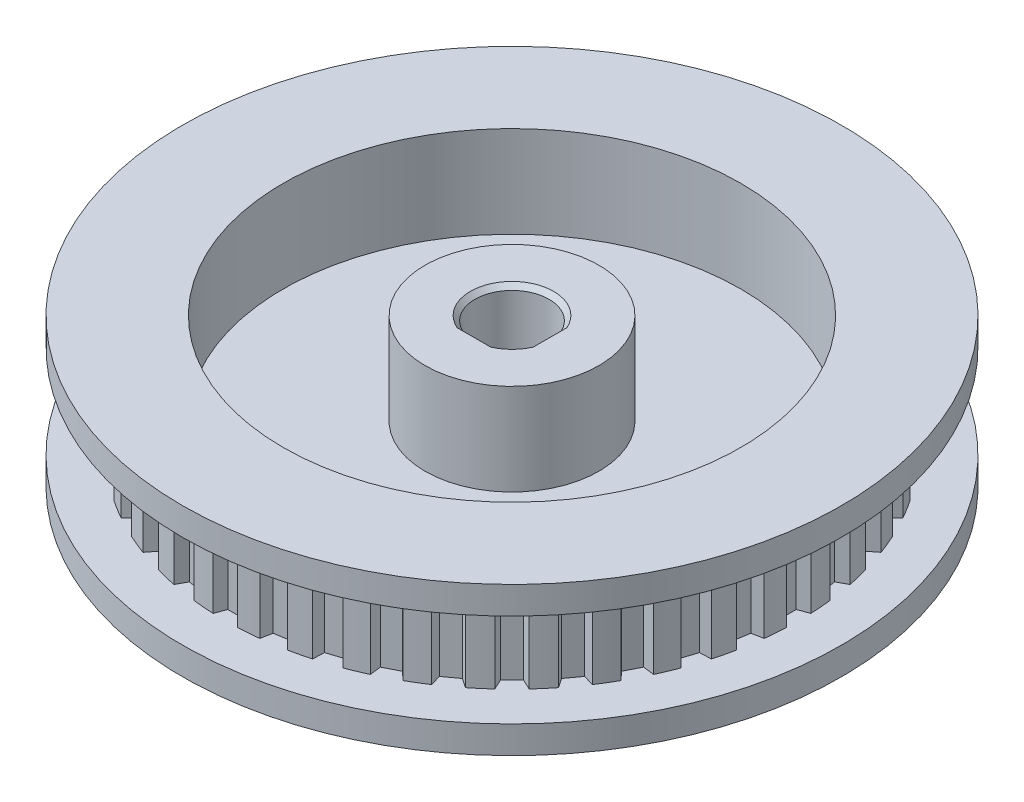
SolidWorks part; units mm, degrees
ref_plane "Спереди" through (0, 0, 0) normal (0, 0, 1) x (1, 0, 0)
ref_plane "Сверху" through (0, 0, 0) normal (0, 1, 0) x (1, 0, 0)
ref_plane "Справа" through (0, 0, 0) normal (1, 0, 0) x (0, 0, -1)
sketch "Эскиз1" plane through (0, 0, 0) normal (0, 1, 0) x (1, 0, 0)
  line L0 (0, 32.35) -> (0, 0) construction
  line L1 (-0.9, 30.15) -> (0.9, 30.15)
  line L2 (-0.9, 30.15) -> (-1.3265, 31.3219)
  line L3 (0.9, 30.15) -> (1.3265, 31.3219)
  line L4 (3.8276, 29.9196) -> (3.5896, 31.1438)
  line L5 (3.8276, 29.9196) -> (5.6054, 29.638)
  line L6 (5.6054, 29.638) -> (6.21, 30.7288)
  line L7 (8.4609, 28.9525) -> (8.4174, 30.1988)
  line L8 (8.4609, 28.9525) -> (10.1728, 28.3962)
  line L9 (10.1728, 28.3962) -> (10.9406, 29.379)
  line L10 (12.8859, 27.2724) -> (13.0379, 28.5103)
  line L11 (12.8859, 27.2724) -> (14.4897, 26.4553)
  line L12 (14.4897, 26.4553) -> (15.4018, 27.3058)
  line L13 (16.9936, 24.9209) -> (17.3374, 26.1197)
  line L14 (16.9936, 24.9209) -> (18.4498, 23.8629)
  line L15 (18.4498, 23.8629) -> (19.4838, 24.5602)
  line L16 (20.6829, 21.9557) -> (21.2099, 23.086)
  line L17 (20.6829, 21.9557) -> (21.9557, 20.6829)
  line L18 (21.9557, 20.6829) -> (23.086, 21.2099)
  line L19 (23.8629, 18.4498) -> (24.5602, 19.4838)
  line L20 (23.8629, 18.4498) -> (24.9209, 16.9936)
  line L21 (24.9209, 16.9936) -> (26.1197, 17.3374)
  line L22 (26.4553, 14.4897) -> (27.3058, 15.4018)
  line L23 (26.4553, 14.4897) -> (27.2724, 12.8859)
  line L24 (27.2724, 12.8859) -> (28.5103, 13.0379)
  line L25 (28.3962, 10.1728) -> (29.379, 10.9406)
  line L26 (28.3962, 10.1728) -> (28.9525, 8.4609)
  line L27 (28.9525, 8.4609) -> (30.1988, 8.4174)
  line L28 (29.638, 5.6054) -> (30.7288, 6.21)
  line L29 (29.638, 5.6054) -> (29.9196, 3.8276)
  line L30 (29.9196, 3.8276) -> (31.1438, 3.5896)
  line L31 (30.15, 0.9) -> (31.3219, 1.3265)
  line L32 (30.15, 0.9) -> (30.15, -0.9)
  line L33 (30.15, -0.9) -> (31.3219, -1.3265)
  line L34 (29.9196, -3.8276) -> (31.1438, -3.5896)
  line L35 (29.9196, -3.8276) -> (29.638, -5.6054)
  line L36 (29.638, -5.6054) -> (30.7288, -6.21)
  line L37 (28.9525, -8.4609) -> (30.1988, -8.4174)
  line L38 (28.9525, -8.4609) -> (28.3962, -10.1728)
  line L39 (28.3962, -10.1728) -> (29.379, -10.9406)
  line L40 (27.2724, -12.8859) -> (28.5103, -13.0379)
  line L41 (27.2724, -12.8859) -> (26.4553, -14.4897)
  line L42 (26.4553, -14.4897) -> (27.3058, -15.4018)
  line L43 (24.9209, -16.9936) -> (26.1197, -17.3374)
  line L44 (24.9209, -16.9936) -> (23.8629, -18.4498)
  line L45 (23.8629, -18.4498) -> (24.5602, -19.4838)
  line L46 (21.9557, -20.6829) -> (23.086, -21.2099)
  line L47 (21.9557, -20.6829) -> (20.6829, -21.9557)
  line L48 (20.6829, -21.9557) -> (21.2099, -23.086)
  line L49 (18.4498, -23.8629) -> (19.4838, -24.5602)
  line L50 (18.4498, -23.8629) -> (16.9936, -24.9209)
  line L51 (16.9936, -24.9209) -> (17.3374, -26.1197)
  line L52 (14.4897, -26.4553) -> (15.4018, -27.3058)
  line L53 (14.4897, -26.4553) -> (12.8859, -27.2724)
  line L54 (12.8859, -27.2724) -> (13.0379, -28.5103)
  line L55 (10.1728, -28.3962) -> (10.9406, -29.379)
  line L56 (10.1728, -28.3962) -> (8.4609, -28.9525)
  line L57 (8.4609, -28.9525) -> (8.4174, -30.1988)
  line L58 (5.6054, -29.638) -> (6.21, -30.7288)
  line L59 (5.6054, -29.638) -> (3.8276, -29.9196)
  line L60 (3.8276, -29.9196) -> (3.5896, -31.1438)
  line L61 (0.9, -30.15) -> (1.3265, -31.3219)
  line L62 (0.9, -30.15) -> (-0.9, -30.15)
  line L63 (-0.9, -30.15) -> (-1.3265, -31.3219)
  line L64 (-3.8276, -29.9196) -> (-3.5896, -31.1438)
  line L65 (-3.8276, -29.9196) -> (-5.6054, -29.638)
  line L66 (-5.6054, -29.638) -> (-6.21, -30.7288)
  line L67 (-8.4609, -28.9525) -> (-8.4174, -30.1988)
  line L68 (-8.4609, -28.9525) -> (-10.1728, -28.3962)
  line L69 (-10.1728, -28.3962) -> (-10.9406, -29.379)
  line L70 (-12.8859, -27.2724) -> (-13.0379, -28.5103)
  line L71 (-12.8859, -27.2724) -> (-14.4897, -26.4553)
  line L72 (-14.4897, -26.4553) -> (-15.4018, -27.3058)
  line L73 (-16.9936, -24.9209) -> (-17.3374, -26.1197)
  line L74 (-16.9936, -24.9209) -> (-18.4498, -23.8629)
  line L75 (-18.4498, -23.8629) -> (-19.4838, -24.5602)
  line L76 (-20.6829, -21.9557) -> (-21.2099, -23.086)
  line L77 (-20.6829, -21.9557) -> (-21.9557, -20.6829)
  line L78 (-21.9557, -20.6829) -> (-23.086, -21.2099)
  line L79 (-23.8629, -18.4498) -> (-24.5602, -19.4838)
  line L80 (-23.8629, -18.4498) -> (-24.9209, -16.9936)
  line L81 (-24.9209, -16.9936) -> (-26.1197, -17.3374)
  line L82 (-26.4553, -14.4897) -> (-27.3058, -15.4018)
  line L83 (-26.4553, -14.4897) -> (-27.2724, -12.8859)
  line L84 (-27.2724, -12.8859) -> (-28.5103, -13.0379)
  line L85 (-28.3962, -10.1728) -> (-29.379, -10.9406)
  line L86 (-28.3962, -10.1728) -> (-28.9525, -8.4609)
  line L87 (-28.9525, -8.4609) -> (-30.1988, -8.4174)
  line L88 (-29.638, -5.6054) -> (-30.7288, -6.21)
  line L89 (-29.638, -5.6054) -> (-29.9196, -3.8276)
  line L90 (-29.9196, -3.8276) -> (-31.1438, -3.5896)
  line L91 (-30.15, -0.9) -> (-31.3219, -1.3265)
  line L92 (-30.15, -0.9) -> (-30.15, 0.9)
  line L93 (-30.15, 0.9) -> (-31.3219, 1.3265)
  line L94 (-29.9196, 3.8276) -> (-31.1438, 3.5896)
  line L95 (-29.9196, 3.8276) -> (-29.638, 5.6054)
  line L96 (-29.638, 5.6054) -> (-30.7288, 6.21)
  line L97 (-28.9525, 8.4609) -> (-30.1988, 8.4174)
  line L98 (-28.9525, 8.4609) -> (-28.3962, 10.1728)
  line L99 (-28.3962, 10.1728) -> (-29.379, 10.9406)
  line L100 (-27.2724, 12.8859) -> (-28.5103, 13.0379)
  line L101 (-27.2724, 12.8859) -> (-26.4553, 14.4897)
  line L102 (-26.4553, 14.4897) -> (-27.3058, 15.4018)
  line L103 (-24.9209, 16.9936) -> (-26.1197, 17.3374)
  line L104 (-24.9209, 16.9936) -> (-23.8629, 18.4498)
  line L105 (-23.8629, 18.4498) -> (-24.5602, 19.4838)
  line L106 (-21.9557, 20.6829) -> (-23.086, 21.2099)
  line L107 (-21.9557, 20.6829) -> (-20.6829, 21.9557)
  line L108 (-20.6829, 21.9557) -> (-21.2099, 23.086)
  line L109 (-18.4498, 23.8629) -> (-19.4838, 24.5602)
  line L110 (-18.4498, 23.8629) -> (-16.9936, 24.9209)
  line L111 (-16.9936, 24.9209) -> (-17.3374, 26.1197)
  line L112 (-14.4897, 26.4553) -> (-15.4018, 27.3058)
  line L113 (-14.4897, 26.4553) -> (-12.8859, 27.2724)
  line L114 (-12.8859, 27.2724) -> (-13.0379, 28.5103)
  line L115 (-10.1728, 28.3962) -> (-10.9406, 29.379)
  line L116 (-10.1728, 28.3962) -> (-8.4609, 28.9525)
  line L117 (-8.4609, 28.9525) -> (-8.4174, 30.1988)
  line L118 (-5.6054, 29.638) -> (-6.21, 30.7288)
  line L119 (-5.6054, 29.638) -> (-3.8276, 29.9196)
  line L120 (-3.8276, 29.9196) -> (-3.5896, 31.1438)
  circle A0 centre (0, 0) radius 30.15 construction
  circle A1 centre (0, 0) radius 32.35 construction
  circle A2 centre (0, 0) radius 31.85 construction
  circle A3 centre (0, 0) radius 31.35 construction
  arc A4 (-3.5896, 31.1438) -> (-1.3265, 31.3219) centre (0, 0) cw
  arc A5 (1.3265, 31.3219) -> (3.5896, 31.1438) centre (0, 0) cw
  arc A6 (6.21, 30.7288) -> (8.4174, 30.1988) centre (0, 0) cw
  arc A7 (10.9406, 29.379) -> (13.0379, 28.5103) centre (0, 0) cw
  arc A8 (15.4018, 27.3058) -> (17.3374, 26.1197) centre (0, 0) cw
  arc A9 (19.4838, 24.5602) -> (21.2099, 23.086) centre (0, 0) cw
  arc A10 (23.086, 21.2099) -> (24.5602, 19.4838) centre (0, 0) cw
  arc A11 (26.1197, 17.3374) -> (27.3058, 15.4018) centre (0, 0) cw
  arc A12 (28.5103, 13.0379) -> (29.379, 10.9406) centre (0, 0) cw
  arc A13 (30.1988, 8.4174) -> (30.7288, 6.21) centre (0, 0) cw
  arc A14 (31.1438, 3.5896) -> (31.3219, 1.3265) centre (0, 0) cw
  arc A15 (31.3219, -1.3265) -> (31.1438, -3.5896) centre (0, 0) cw
  arc A16 (30.7288, -6.21) -> (30.1988, -8.4174) centre (0, 0) cw
  arc A17 (29.379, -10.9406) -> (28.5103, -13.0379) centre (0, 0) cw
  arc A18 (27.3058, -15.4018) -> (26.1197, -17.3374) centre (0, 0) cw
  arc A19 (24.5602, -19.4838) -> (23.086, -21.2099) centre (0, 0) cw
  arc A20 (21.2099, -23.086) -> (19.4838, -24.5602) centre (0, 0) cw
  arc A21 (17.3374, -26.1197) -> (15.4018, -27.3058) centre (0, 0) cw
  arc A22 (13.0379, -28.5103) -> (10.9406, -29.379) centre (0, 0) cw
  arc A23 (8.4174, -30.1988) -> (6.21, -30.7288) centre (0, 0) cw
  arc A24 (3.5896, -31.1438) -> (1.3265, -31.3219) centre (0, 0) cw
  arc A25 (-1.3265, -31.3219) -> (-3.5896, -31.1438) centre (0, 0) cw
  arc A26 (-6.21, -30.7288) -> (-8.4174, -30.1988) centre (0, 0) cw
  arc A27 (-10.9406, -29.379) -> (-13.0379, -28.5103) centre (0, 0) cw
  arc A28 (-15.4018, -27.3058) -> (-17.3374, -26.1197) centre (0, 0) cw
  arc A29 (-19.4838, -24.5602) -> (-21.2099, -23.086) centre (0, 0) cw
  arc A30 (-23.086, -21.2099) -> (-24.5602, -19.4838) centre (0, 0) cw
  arc A31 (-26.1197, -17.3374) -> (-27.3058, -15.4018) centre (0, 0) cw
  arc A32 (-28.5103, -13.0379) -> (-29.379, -10.9406) centre (0, 0) cw
  arc A33 (-30.1988, -8.4174) -> (-30.7288, -6.21) centre (0, 0) cw
  arc A34 (-31.1438, -3.5896) -> (-31.3219, -1.3265) centre (0, 0) cw
  arc A35 (-31.3219, 1.3265) -> (-31.1438, 3.5896) centre (0, 0) cw
  arc A36 (-30.7288, 6.21) -> (-30.1988, 8.4174) centre (0, 0) cw
  arc A37 (-29.379, 10.9406) -> (-28.5103, 13.0379) centre (0, 0) cw
  arc A38 (-27.3058, 15.4018) -> (-26.1197, 17.3374) centre (0, 0) cw
  arc A39 (-24.5602, 19.4838) -> (-23.086, 21.2099) centre (0, 0) cw
  arc A40 (-21.2099, 23.086) -> (-19.4838, 24.5602) centre (0, 0) cw
  arc A41 (-17.3374, 26.1197) -> (-15.4018, 27.3058) centre (0, 0) cw
  arc A42 (-13.0379, 28.5103) -> (-10.9406, 29.379) centre (0, 0) cw
  arc A43 (-8.4174, 30.1988) -> (-6.21, 30.7288) centre (0, 0) cw
  point P6 (0, 30.15)
  dimension "D1" = 63.7
  dimension "D2" = 64.7
  dimension "D3" = 60.3
  dimension "D4" = 62.7
  dimension "D5" = 1.8
  dimension "D6" = 20
  dimension "D7" = 20
extrude "Вытянуть1" add sketch "Эскиз1" along normal blind 10.2
sketch "Эскиз2" plane through (0, 10.2, 0) normal (0, 1, 0) x (1, 0, 0)
  circle A0 centre (0, 0) radius 36
  dimension "D1" = 72
extrude "Вытянуть2" add sketch "Эскиз2" along normal blind 3
sketch "Эскиз3" plane through (0, 0, 0) normal (0, -1, 0) x (1, 0, 0)
  circle A0 centre (0, 0) radius 36
  circle A1 centre (0, 0) radius 36 construction
extrude "Вытянуть3" add sketch "Эскиз3" along normal blind 3
sketch "Эскиз4" plane through (0, 13.2, 0) normal (0, 1, 0) x (1, 0, 0)
  circle A0 centre (0, 0) radius 25
  circle A1 centre (0, 0) radius 9.5
  dimension "D1" = 50
  dimension "D2" = 19
extrude "Вытянуть4" cut sketch "Эскиз4" against normal blind 10
sketch "Эскиз5" plane through (0, 13.2, 0) normal (0, 1, 0) x (1, 0, 0)
  line L0 (3.6643, 1.725) -> (3.6643, -1.725)
  line L1 (1.725, -3.6643) -> (-1.725, -3.6643)
  circle A0 centre (0, 0) radius 4.05 construction
  arc A1 (3.6643, 1.725) -> (-1.725, -3.6643) centre (0, 0) ccw
  arc A2 (1.725, -3.6643) -> (3.6643, -1.725) centre (0, 0) ccw
  dimension "D1" = 8.1
  dimension "D2" = 3.45
extrude "Вытянуть5" cut sketch "Эскиз5" against normal blind 10
sketch "Эскиз6" plane through (0, -3, 0) normal (0, -1, 0) x (1, 0, 0)
  circle A0 centre (0, 0) radius 4.05
  dimension "D1" = 8.1
extrude "Вытянуть6" cut sketch "Эскиз6" against normal up to surface (6.2 mm away) up to face at (0.9161, 3.2, 0.9161)
chamfer "Фаска1" distance 0.5 angle 45 1 edges at (0, -3, -4.05)
chamfer "Фаска2" distance 0.5 angle 45 4 edges at (0, 13.2, 3.6643) (2.8638, 13.2, 2.8638) (3.6643, 13.2, 0) (-2.8638, 13.2, -2.8638)
